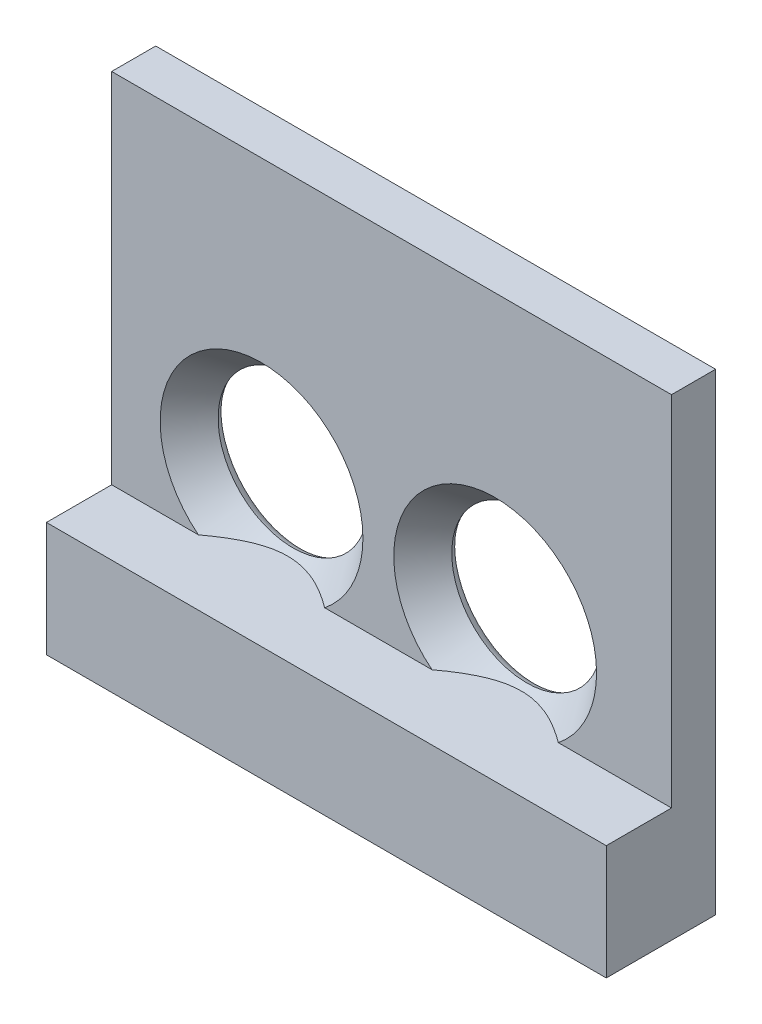
SolidWorks part; units mm, degrees
ref_plane "Přední rovina" through (0, 0, 0) normal (0, 0, 1) x (1, 0, 0)
ref_plane "Horní rovina" through (0, 0, 0) normal (0, 1, 0) x (1, 0, 0)
ref_plane "Pravá rovina" through (0, 0, 0) normal (1, 0, 0) x (0, 0, -1)
sketch "Skica2" plane through (0, 0, 0) normal (0, 0, 1) x (1, 0, 0)
  line L1 (-25.5382, 62.1313) -> (37.9618, 62.1313)
  line L2 (-25.5382, 62.1313) -> (-25.5382, 8.5313)
  line L3 (-25.5382, 8.5313) -> (37.9618, 8.5313)
  line L4 (37.9618, 62.1313) -> (37.9618, 8.5313)
  dimension "D1" = 53.6
  dimension "D2" = 63.5
extrude "Přidat vysunutím1" add sketch "Skica2" along normal blind 5
sketch "Skica3" plane through (0, 0, 5) normal (0, 0, 1) x (1, 0, 0)
  line L0 (37.9618, 8.5313) -> (37.9618, 62.1313) construction
  line L1 (-25.5382, 8.5313) -> (37.9618, 8.5313)
  line L2 (-25.5382, 8.5313) -> (-25.5382, 21.5313)
  line L3 (-25.5382, 21.5313) -> (37.9618, 21.5313)
  line L4 (37.9618, 8.5313) -> (37.9618, 21.5313)
  dimension "D1" = 13
extrude "Přidat vysunutím2" add sketch "Skica3" along normal blind 7.4
sketch "Skica5" plane through (0, 0, 0) normal (0, 0, -1) x (-1, 0, 0)
  line L0 (-37.9618, 48.5313) -> (25.5382, 48.5313) construction
  line L1 (-37.9618, 8.5313) -> (-37.9618, 62.1313) construction
  line L2 (25.5382, 62.1313) -> (25.5382, 8.5313) construction
  line L3 (25.5382, 8.5313) -> (-37.9618, 8.5313) construction
  line L4 (-37.9618, 30.5313) -> (47.0935, 30.5313) construction
  line L5 (-17.9618, 30.5313) -> (-17.9618, 48.5313) construction
  line L6 (8.5382, 30.5313) -> (8.5382, 75.1414) construction
  circle A0 centre (-17.9618, 30.5313) radius 8.5
  circle A1 centre (8.5382, 30.5313) radius 8.5
  point P16 (47.0935, 30.5313)
  point P17 (8.5382, 75.1414)
  dimension "D6" = 17
  dimension "D1" = 40
  dimension "D2" = 18
  dimension "D3" = 20
  dimension "D4" = 17
  dimension "D5" = 26.5
extrude "Odebrat vysunutím1" cut sketch "Skica5" against normal blind 74
chamfer "Zkosení1" distance 3 angle 50 2 edges at (26.4618, 30.5313, 5) (-0.0382, 30.5313, 5) first distance on face at (26.4618, 30.5313, 5)
fillet "Zaoblit1" radius 2 2 edges at (9.4618, 30.5313, 0) (-17.0382, 30.5313, 0)
